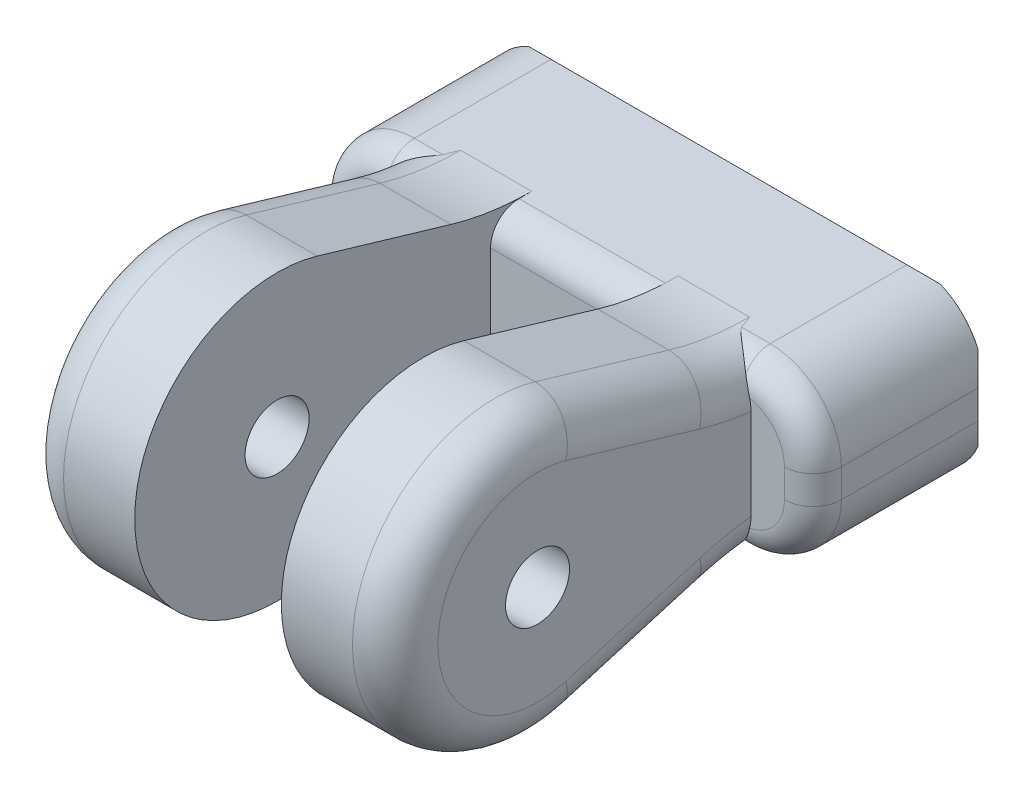
SolidWorks part; units mm, degrees
ref_plane "Front Plane" through (0, 0, 0) normal (0, 0, 1) x (1, 0, 0)
ref_plane "Top Plane" through (0, 0, 0) normal (0, 1, 0) x (1, 0, 0)
ref_plane "Right Plane" through (0, 0, 0) normal (1, 0, 0) x (0, 0, -1)
sketch "Sketch1" plane through (0, 0, 0) normal (0, 0, 1) x (1, 0, 0)
  line L0 (0, 0) -> (0, 31.117) construction
  line L4 (-17.5, -6) -> (17.5, -6)
  line L5 (-17.5, -6) -> (-17.5, 6)
  line L6 (-17.5, 6) -> (17.5, 6)
  line L7 (17.5, -6) -> (17.5, 6)
  line L8 (-17.5, -6) -> (17.5, 6) construction
  line L9 (-17.5, 6) -> (17.5, -6) construction
  circle A0 centre (11, 0) radius 4.25
  circle A1 centre (-11, 0) radius 4.25
  dimension "D1" = 8.5
  dimension "D3" = 12
  dimension "D2" = 22
  dimension "D4" = 35
extrude "Boss-Extrude1" add sketch "Sketch1" along normal mid plane 12
sketch "Sketch5" plane through (0, 0, 6) normal (0, 0, 1) x (1, 0, 0)
  circle A0 centre (-11, 0) radius 4.25
  circle A1 centre (-11, 0) radius 4.25 construction
  circle A2 centre (11, 0) radius 4.25
  circle A3 centre (11, 0) radius 4.25 construction
extrude "Boss-Extrude3" add sketch "Sketch5" against normal blind 3
sketch "Sketch6" plane through (0, 0, 0) normal (1, 0, 0) x (0, 0, -1)
  line L0 (-6, 6) -> (-18.1698, 9.5911)
  line L1 (0, 0) -> (16.6175, 0) construction
  line L2 (-6, -6) -> (-18.1698, -9.5911)
  line L3 (-6, 6) -> (-6, -6)
  circle A0 centre (-21, 0) radius 10
  circle A1 centre (-21, 0) radius 2.25
  dimension "D1" = 20
  dimension "D3" = 4.5
  dimension "D2" = 21
extrude "Boss-Extrude4" add sketch "Sketch6" along normal blind 8 from offset 5.15 contours A0 L2 L3 L0 | A0 A1 region at (0, 0, 9.5342) region at (0, 5.818, 13.2171)
mirror "Mirror2" about plane through (0, 0, 0) normal (1, 0, 0) of "Boss-Extrude4"
fillet "Fillet1" radius 20 4 edges at (-9.15, -6, 6) (9.15, -6, 6) (-9.15, 6, 6) (9.15, 6, 6)
fillet "Fillet2" radius 3 10 edges at (-13.15, -8.2044, 13.4705) (-13.15, 0, 31) (13.15, -8.2044, 13.4705) (13.15, 0, 31) (-13.15, 8.2044, 13.4705) (13.15, 8.2044, 13.4705) (-13.15, 6.2055, 5.9703) (-13.15, -6.2055, 5.9703) (13.15, 6.2055, 5.9703) (13.15, -6.2055, 5.9703)
chamfer "Chamfer1" distance 0.4 angle 45 6 edges at (-15.25, 0, -6) (0, -6, -6) (17.5, 0, -6) (0, 6, -6) (-17.5, 0, -6) (15.25, 0, -6)
fillet "Fillet3" radius 5 4 edges at (17.5, -6, 0.2) (17.5, 6, 0.2) (-17.5, -6, 0.2) (-17.5, 6, 0.2)
fillet "Fillet4" radius 2 12 edges at (11.8733, -6, 6) (16.0355, -4.5355, 6) (17.5, 0, 6) (11.8733, 6, 6) (-11.8733, 6, 6) (-11.8733, -6, 6) (-16.0355, -4.5355, 6) (-17.5, 0, 6) (0, -6, 6) (0, 6, 6) (16.0355, 4.5355, 6) (-16.0355, 4.5355, 6)
sketch "Sketch7" plane through (0, 0, 3) normal (0, 0, -1) x (-1, 0, 0)
  line L0 (15.65, 0) -> (6.35, 0)
  circle A0 centre (11, 0) radius 4.65 construction
  arc A1 (6.35, 0) -> (15.65, 0) centre (11, 0) ccw
extrude "Boss-Extrude5" add sketch "Sketch7" along normal blind 9
sketch "Sketch8" plane through (0, 0, 3) normal (0, 0, -1) x (-1, 0, 0)
  line L0 (-11, 0) -> (-6.35, 0)
  line L1 (-11, 0) -> (-15.65, 0)
  circle A2 centre (-11, 0) radius 4.65 construction
  arc A3 (-15.65, 0) -> (-6.35, 0) centre (-11, 0) ccw
extrude "Boss-Extrude7" add sketch "Sketch8" along normal blind 9
